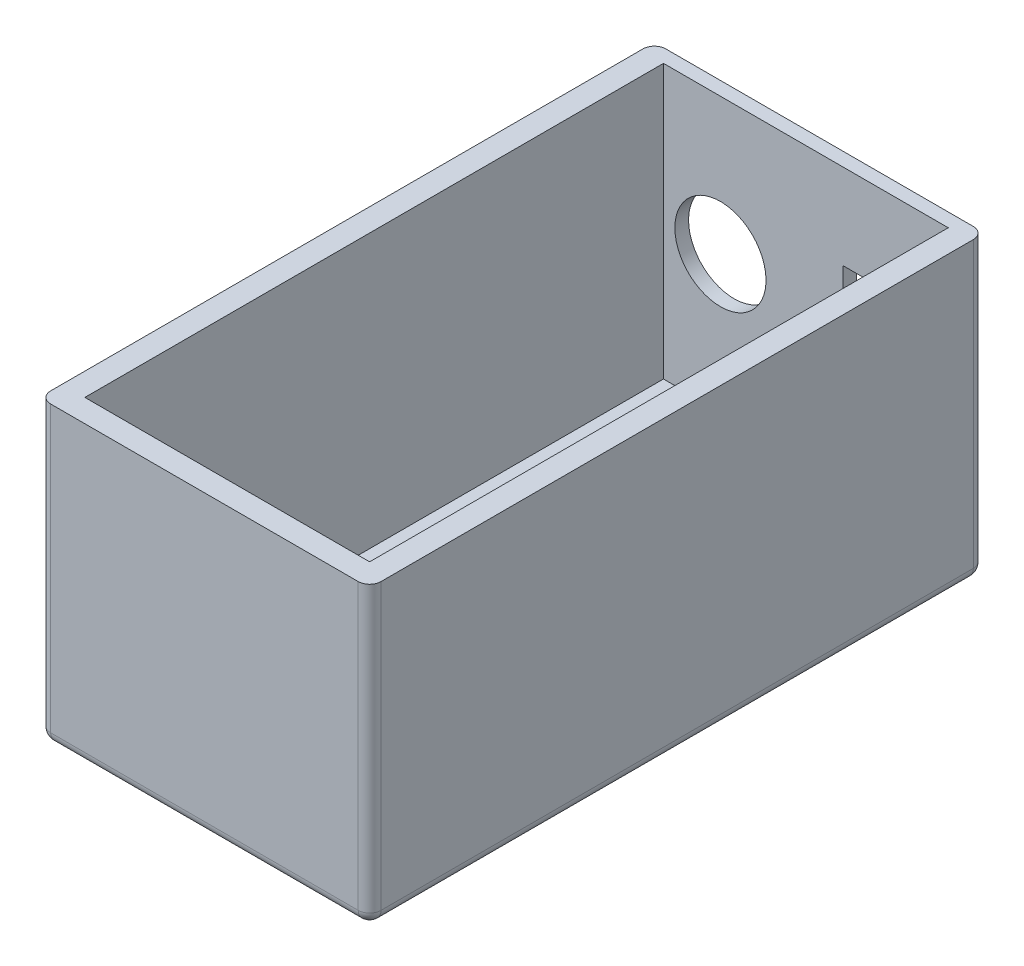
SolidWorks part; units mm, degrees
ref_plane "Front Plane" through (0, 0, 0) normal (0, 0, 1) x (1, 0, 0)
ref_plane "Top Plane" through (0, 0, 0) normal (0, 1, 0) x (1, 0, 0)
ref_plane "Right Plane" through (0, 0, 0) normal (1, 0, 0) x (0, 0, -1)
sketch "Sketch1" plane through (0, 0, 0) normal (0, 1, 0) x (1, 0, 0)
  line L0 (-14.5, -27) -> (-14.5, 27)
  line L1 (-12.5, -25) -> (12.5, -25)
  line L2 (-12.5, -25) -> (-12.5, 25)
  line L3 (-12.5, 25) -> (12.5, 25)
  line L4 (12.5, -25) -> (12.5, 25)
  line L5 (-12.5, -25) -> (12.5, 25) construction
  line L6 (-12.5, 25) -> (12.5, -25) construction
  line L7 (-14.5, 27) -> (14.5, 27)
  line L8 (14.5, -27) -> (14.5, 27)
  line L9 (-14.5, -27) -> (14.5, -27)
  point P0 (0, 0)
  dimension "D1" = 25
  dimension "D2" = 50
  dimension "D3" = 2
extrude "Boss-Extrude1" add sketch "Sketch1" along normal blind 24
sketch "Sketch2" plane through (0, 0, 0) normal (0, -1, 0) x (1, 0, 0)
  line L0 (14.5, -27) -> (-14.5, -27) construction
  line L1 (-14.5, -27) -> (-14.5, 27) construction
  line L2 (-14.5, 27) -> (14.5, 27) construction
  line L3 (14.5, 27) -> (14.5, -27) construction
  line L4 (14.5, -27) -> (-14.5, -27)
  line L5 (-14.5, -27) -> (-14.5, 27)
  line L6 (-14.5, 27) -> (14.5, 27)
  line L7 (14.5, 27) -> (14.5, -27)
extrude "Boss-Extrude2" add sketch "Sketch2" along normal blind 2
sketch "Sketch3" plane through (0, 0, -27) normal (0, 0, -1) x (-1, 0, 0)
  line L0 (-12.5, 24) -> (-12.5, 0) construction
  line L1 (-6.75, 7.5) -> (-3.25, 7.5)
  line L2 (-6.75, 7.5) -> (-6.75, 16.5)
  line L3 (-6.75, 16.5) -> (-3.25, 16.5)
  line L4 (-3.25, 7.5) -> (-3.25, 16.5)
  line L5 (-6.75, 7.5) -> (-3.25, 16.5) construction
  line L6 (-6.75, 16.5) -> (-3.25, 7.5) construction
  line L7 (-12.5, 24) -> (-12.5, 0) construction
  line L8 (12.5, 24) -> (12.5, 0) construction
  line L9 (12.5, 24) -> (12.5, 0) construction
  line L10 (-12.5, 0) -> (12.5, 0) construction
  line L11 (-12.5, 0) -> (12.5, 0) construction
  circle A0 centre (7.5, 12) radius 4
  point P0 (-5, 12)
  dimension "D5" = 8
  dimension "D1" = 3.5
  dimension "D2" = 9
  dimension "D3" = 12
  dimension "D4" = 7.5
  dimension "D6" = 12.5
  dimension "D7" = 12
extrude "Cut-Extrude1" cut sketch "Sketch3" against normal up to next
sketch "Sketch6" plane through (0, 0, -25) normal (0, 0, 1) x (1, 0, 0)
  line L24 (-12.5, 0) -> (12.5, 0)
  line L25 (12.5, 0) -> (12.5, 24)
  line L26 (12.5, 24) -> (-12.5, 24)
  line L27 (-12.5, 24) -> (-12.5, 0)
  line L28 (-12.5, 0) -> (12.5, 0)
  line L29 (12.5, 0) -> (12.5, 24)
  line L30 (12.5, 24) -> (-12.5, 24)
  line L31 (-12.5, 24) -> (-12.5, 0)
  circle A0 centre (-7.5, 12) radius 4 construction
  circle A1 centre (-7.5, 12) radius 4 construction
  dimension "D1" = 0
extrude "Cut-Extrude4" cut sketch "Sketch6" against normal blind 0.8
fillet "Fillet1" radius 1 8 edges at (0, -2, -27) (-14.5, -2, 0) (0, -2, 27) (14.5, -2, 0) (14.5, 11, 27) (-14.5, 11, 27) (-14.5, 11, -27) (14.5, 11, -27)
